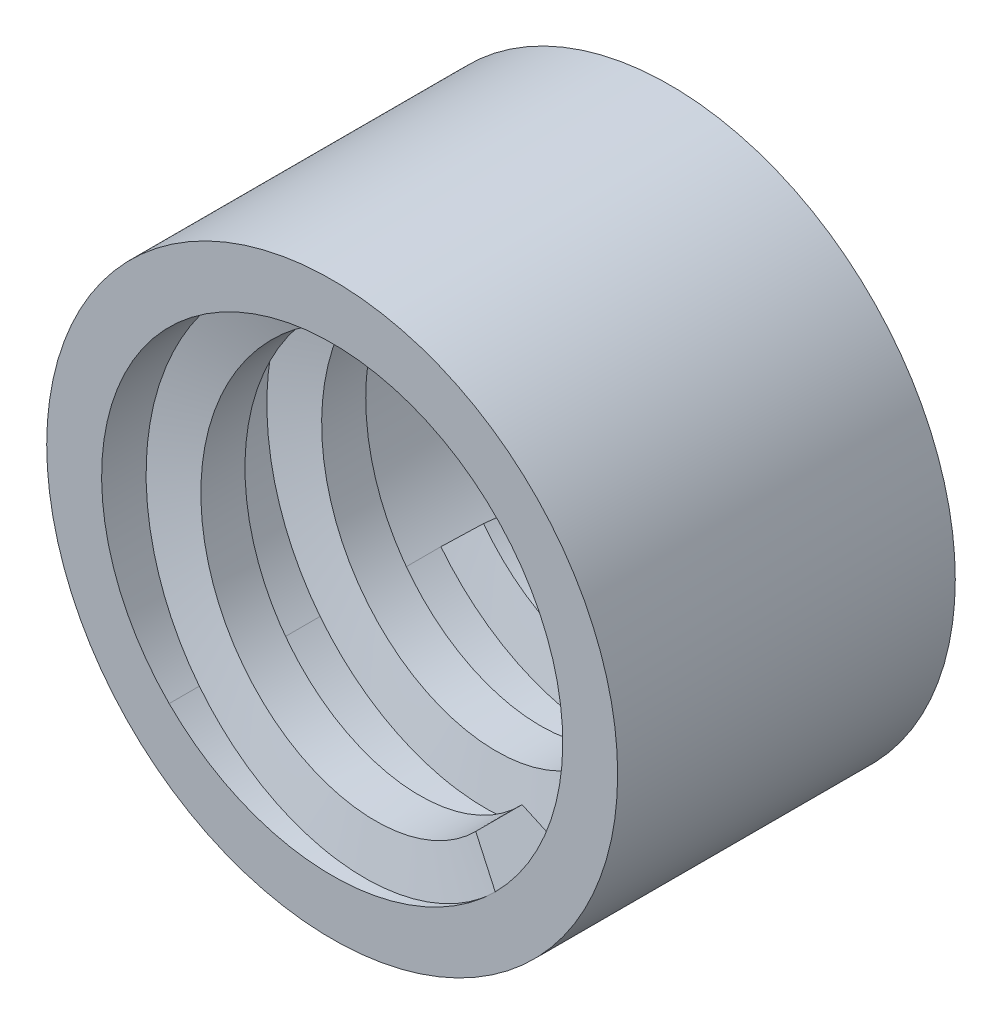
SolidWorks part; units mm, degrees
ref_plane "前视基准面" through (0, 0, 0) normal (0, 0, 1) x (1, 0, 0)
ref_plane "上视基准面" through (0, 0, 0) normal (0, 1, 0) x (1, 0, 0)
ref_plane "右视基准面" through (0, 0, 0) normal (1, 0, 0) x (0, 0, -1)
sketch "草图1" plane through (0, 0, 0) normal (0, 0, 1) x (1, 0, 0)
  circle A0 centre (0, 0) radius 13
extrude "凸台-拉伸1" add sketch "草图1" along normal blind 12.375 and the other way blind 3
sketch "草图2" plane through (0, 0, 0) normal (0, 0, 1) x (1, 0, 0)
  circle A0 centre (0, 0) radius 10.5
extrude "切除-拉伸1" cut sketch "草图2" against normal blind 10 and the other way blind 20
sketch "草图3" plane through (0, 0, 0) normal (0, 0, 1) x (1, 0, 0)
  circle A0 centre (0, 0) radius 10.5
curve "螺旋线/涡状线1" pitch 5.5 height 12.375 radius 10.5 centre (0, 0, 0) axis (0, 0, 1) start towards (1, 0, 0)
ref_plane "基准面1" through (-7.4246, -7.4246, 0) normal (0.7047, -0.7047, 0.0831) x (0.0587, -0.0587, -0.9965)
sketch "草图4" plane through (-7.4246, -7.4246, 0) normal (0.7047, -0.7047, 0.0831) x (0.0587, -0.0587, -0.9965)
  line L0 (0, 0) -> (3, 0)
  line L1 (0.5, 2) -> (2.5, 2)
  line L2 (2.5, 2) -> (3, 0)
  line L3 (0.5, 2) -> (0, 0)
  line L4 (0, 0) -> (-0.108, 0.0401)
sweep "扫描1" add profiles "草图4" path "螺旋线/涡状线1"
